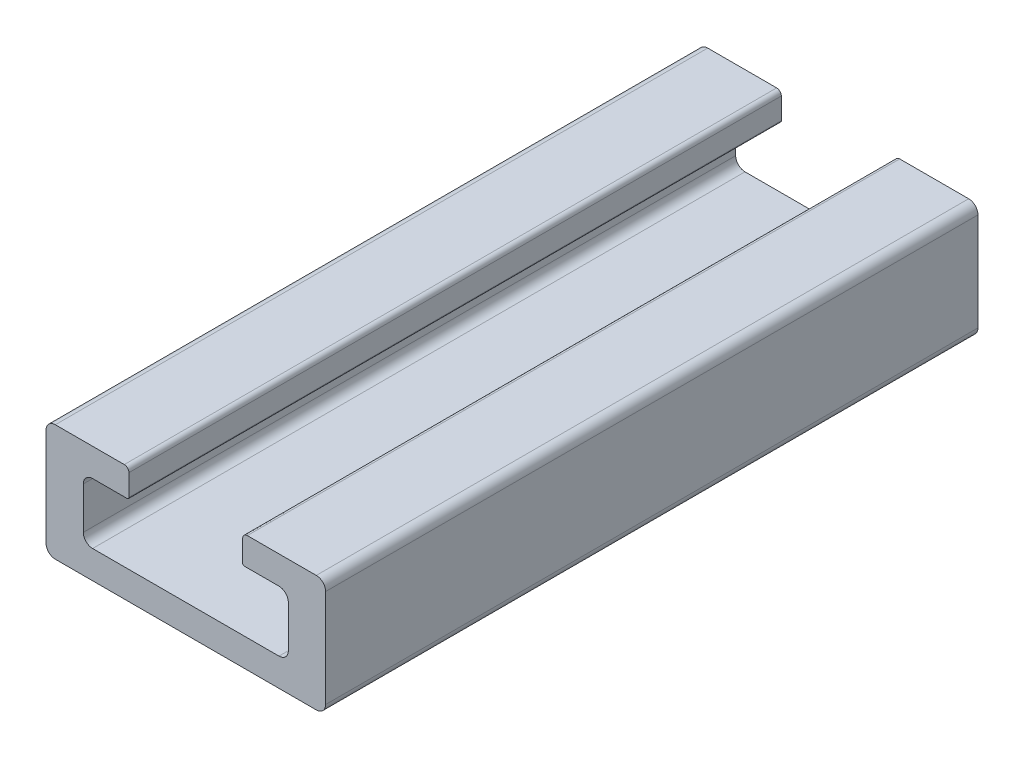
SolidWorks part; units mm, degrees
ref_plane "Front Plane" through (0, 0, 0) normal (0, 0, 1) x (1, 0, 0)
ref_plane "Top Plane" through (0, 0, 0) normal (0, 1, 0) x (1, 0, 0)
ref_plane "Right Plane" through (0, 0, 0) normal (1, 0, 0) x (0, 0, -1)
ref_plane "Plane1" through (0, 0, 0) normal (0, 0, 1) x (1, 0, 0)
sketch "Sketch1" plane through (0, 0, 0) normal (0, 0, 1) x (1, 0, 0)
  line L0 (-15, 5.25) -> (-15, -5.25)
  line L1 (-14, -6.25) -> (14, -6.25)
  line L2 (15, -5.25) -> (15, 5.25)
  line L3 (14, 6.25) -> (6.6, 6.25)
  line L4 (6.1, 5.75) -> (6.1, 3.45)
  line L5 (6.3, 3.25) -> (10, 3.25)
  line L6 (11, 2.25) -> (11, -2.25)
  line L7 (10, -3.25) -> (-10, -3.25)
  line L8 (-11, -2.25) -> (-11, 2.25)
  line L9 (-10, 3.25) -> (-6.3, 3.25)
  line L10 (-6.1, 3.45) -> (-6.1, 5.75)
  line L11 (-6.6, 6.25) -> (-14, 6.25)
  arc A0 (-15, -5.25) -> (-14, -6.25) centre (-14, -5.25) ccw
  arc A1 (14, -6.25) -> (15, -5.25) centre (14, -5.25) ccw
  arc A2 (15, 5.25) -> (14, 6.25) centre (14, 5.25) ccw
  arc A3 (6.6, 6.25) -> (6.1, 5.75) centre (6.6, 5.75) ccw
  arc A4 (6.1, 3.45) -> (6.3, 3.25) centre (6.3, 3.45) ccw
  arc A5 (10, 3.25) -> (11, 2.25) centre (10, 2.25) cw
  arc A6 (11, -2.25) -> (10, -3.25) centre (10, -2.25) cw
  arc A7 (-10, -3.25) -> (-11, -2.25) centre (-10, -2.25) cw
  arc A8 (-11, 2.25) -> (-10, 3.25) centre (-10, 2.25) cw
  arc A9 (-6.3, 3.25) -> (-6.1, 3.45) centre (-6.3, 3.45) ccw
  arc A10 (-6.1, 5.75) -> (-6.6, 6.25) centre (-6.6, 5.75) ccw
  arc A11 (-14, 6.25) -> (-15, 5.25) centre (-14, 5.25) ccw
extrude "Boss-Extrude1" add sketch "Sketch1" against normal blind 35 and the other way blind 35
ref_plane "Plane2" through (0, 0, 0) normal (1, 0, 0) x (0, 0, -1)
sketch "Sketch2" plane through (0, 0, 0) normal (1, 0, 0) x (0, 0, -1)
  line L0 (-20, -3.25) -> (-17, -3.25)
  line L1 (-17, -3.25) -> (-17, -5.25)
  line L2 (-17, -5.25) -> (-18.25, -5.25)
  line L3 (-18.25, -5.25) -> (-18.25, -6.25)
  line L4 (-18.25, -6.25) -> (-20, -6.25)
  line L5 (-20, -6.25) -> (-20, -3.25)
  line L6 (-20, -6.25) -> (-20, -3.25) construction
revolve "Cut-Revolve1" cut sketch "Sketch2" angle 360 about L6 reverse direction yes
ref_plane "Plane3" through (0, 0, 0) normal (1, 0, 0) x (0, 0, -1)
sketch "Sketch3" plane through (0, 0, 0) normal (1, 0, 0) x (0, 0, -1)
  line L0 (20, -3.25) -> (23, -3.25)
  line L1 (23, -3.25) -> (23, -5.25)
  line L2 (23, -5.25) -> (21.75, -5.25)
  line L3 (21.75, -5.25) -> (21.75, -6.25)
  line L4 (21.75, -6.25) -> (20, -6.25)
  line L5 (20, -6.25) -> (20, -3.25)
  line L6 (20, -6.25) -> (20, -3.25) construction
revolve "Cut-Revolve2" cut sketch "Sketch3" angle 360 about L6 reverse direction yes
